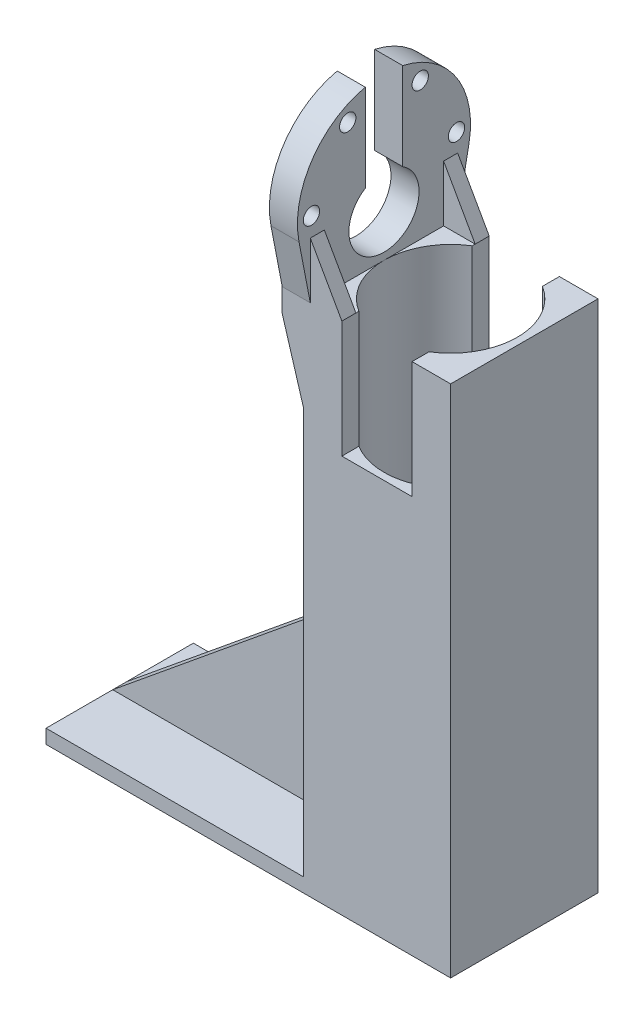
SolidWorks part; units mm, degrees
material "PET"
ref_plane "Front Plane" through (0, 0, 0) normal (0, 0, 1) x (1, 0, 0)
ref_plane "Top Plane" through (0, 0, 0) normal (0, 1, 0) x (1, 0, 0)
ref_plane "Right Plane" through (0, 0, 0) normal (1, 0, 0) x (0, 0, -1)
sketch "Sketch1" plane through (0, 0, 0) normal (0, 1, 0) x (1, 0, 0)
  line L1 (0, 0) -> (31.5, 0)
  line L2 (0, 0) -> (0, -31.5)
  line L3 (0, -31.5) -> (31.5, -31.5)
  line L4 (31.5, 0) -> (31.5, -31.5)
  dimension "D1" = 31.5
  dimension "D5" = 31.5
extrude "Boss-Extrude1" add sketch "Sketch1" along normal blind 110 contours L1 L4 L3 L2
sketch "Sketch2" plane through (0, 110, 0) normal (0, 1, 0) x (1, 0, 0)
  line L0 (0, 0) -> (31.5, 0) construction
  line L1 (31.5, 0) -> (31.5, -31.5) construction
  circle A0 centre (15.75, -15.75) radius 14.25
  dimension "D1" = 28.5
  dimension "D2" = 15.75
  dimension "D3" = 15.75
extrude "Cut-Extrude1" cut sketch "Sketch2" against normal blind 108
sketch "Sketch4" plane through (0, 0, 0) normal (-1, 0, 0) x (0, 0, 1)
  line L0 (0, 110) -> (31.5, 110) construction
  line L1 (0, 110) -> (0, 0) construction
  line L2 (33.9139, 122.4894) -> (31.5, 110)
  line L3 (31.5, 110) -> (25.0371, 110)
  line L4 (-2.4139, 122.4894) -> (0, 110)
  line L5 (0, 110) -> (6.4629, 110)
  arc A0 (33.9139, 122.4894) -> (-2.4139, 122.4894) centre (15.75, 126) ccw
  arc A1 (6.4629, 110) -> (25.0371, 110) centre (15.75, 126) ccw
  dimension "D1" = 37
  dimension "D2" = 16
  dimension "D3" = 15.75
extrude "Boss-Extrude2" add sketch "Sketch4" against normal blind 1.5 contours A0 L4 L5 A1 L3 L2
extrude "Boss-Extrude3" add sketch "Sketch4<3>" against normal blind 1.5
sketch "Sketch4<3>" plane through (0, 0, 0) normal (-1, 0, 0) x (0, 0, 1) same geometry as "Sketch4"
sketch "Sketch6" plane through (0, 0, 31.5) normal (0, 0, 1) x (1, 0, 0)
  line L3 (0, 110) -> (0, 0) construction
  line L4 (0, 90) -> (0, 110)
  line L6 (0, 110) -> (-4.5, 110)
  line L7 (-4.5, 110) -> (-4.5, 105)
  line L8 (-4.5, 105) -> (0, 90)
  dimension "D1" = 4.5
  dimension "D2" = 20
  dimension "D3" = 5
extrude "Boss-Extrude4" add sketch "Sketch6" against normal up to surface (31.5 mm away) up to face at (12.9, 66, 0)
sketch "Sketch10" plane through (0, 0, 0) normal (-1, 0, 0) x (0, 0, 1)
  line L0 (0, 90) -> (0, 0) construction
  line L1 (31.5, 0) -> (0, 0)
  line L2 (31.5, 0) -> (31.5, 3)
  line L3 (31.5, 3) -> (0, 3)
  line L4 (0, 0) -> (0, 3)
  dimension "D1" = 3
extrude "Boss-Extrude5" add sketch "Sketch10" along normal blind 55
ref_plane "Plane1" through (0, 0, 15.75) normal (0, 0, -1) x (-1, 0, 0)
sketch "Sketch9" plane through (0, 110, 0) normal (0, 1, 0) x (1, 0, 0)
  line L0 (1.5, -31.5) -> (31.5, -31.5) construction
  line L1 (23.25, -31.5) -> (8.25, -31.5)
  line L2 (23.25, -31.5) -> (23.25, 0)
  line L3 (23.25, 0) -> (8.25, 0)
  line L4 (8.25, -31.5) -> (8.25, 0)
  line L5 (1.5, 0) -> (31.5, 0) construction
  line L6 (31.5, 0) -> (31.5, -31.5) construction
  dimension "D1" = 15
  dimension "D2" = 23.25
extrude "Cut-Extrude4" cut sketch "Sketch9" against normal blind 25
sketch "Sketch14" plane through (0, 0, 15.75) normal (0, 0, -1) x (-1, 0, 0)
  line L0 (55, 3) -> (0, 48)
  line L1 (0, 90) -> (0, 3) construction
  line L2 (0, 48) -> (0, 3)
  line L3 (0, 3) -> (55, 3)
extrude "Boss-Extrude6" add sketch "Sketch14" along normal mid plane 3
sketch "Sketch15" plane through (0, 0, 31.5) normal (0, 0, 1) x (1, 0, 0)
  line L0 (8.25, 110) -> (1.5, 110)
  line L1 (1.5, 110) -> (1.5, 122)
  line L2 (1.5, 122) -> (8.25, 110)
  dimension "D1" = 12
extrude "Boss-Extrude7" add sketch "Sketch15" against normal blind 3
sketch "Sketch16" plane through (0, 0, 0) normal (0, 0, -1) x (-1, 0, 0)
  line L0 (-8.25, 110) -> (-1.5, 110)
  line L1 (-1.5, 110) -> (-1.5, 122)
  line L2 (-1.5, 122) -> (-8.25, 110)
  dimension "D1" = 12
extrude "Boss-Extrude8" add sketch "Sketch16" against normal blind 3
extrude "Boss-Extrude9" add sketch "Sketch4<4>" along normal blind 4.5
sketch "Sketch4<4>" plane through (0, 0, 0) normal (-1, 0, 0) x (0, 0, 1) same geometry as "Sketch4"
sketch "Sketch7" plane through (1.5, 0, 0) normal (1, 0, 0) x (0, 0, -1)
  circle A0 centre (-15.75, 126) radius 15.5 construction
  circle A1 centre (-31.25, 126) radius 1.75
  circle A2 centre (-23.5, 139.4234) radius 1.75
  circle A3 centre (-8, 139.4234) radius 1.75
  circle A4 centre (-0.25, 126) radius 1.75
  circle A5 centre (-15.75, 119) radius 7.5
  point P13 (-15.75, 126)
  dimension "D1" = 4
  dimension "D2" = 7
  dimension "D3" = 15
extrude "Cut-Extrude3" cut sketch "Sketch7" against normal mid plane 34.5
sketch "Sketch17" plane through (1.5, 0, 0) normal (1, 0, 0) x (0, 0, -1)
  line L1 (-19.75, 123.0141) -> (-11.75, 123.0141)
  line L2 (-19.75, 123.0141) -> (-19.75, 148.0141)
  line L3 (-19.75, 148.0141) -> (-11.75, 148.0141)
  line L4 (-11.75, 123.0141) -> (-11.75, 148.0141)
  line L5 (-15.75, -47.575) -> (-15.75, 47.575) construction
  dimension "D1" = 8
  dimension "D2" = 4
  dimension "D3" = 25
extrude "Cut-Extrude5" cut sketch "Sketch17" against normal blind 10
